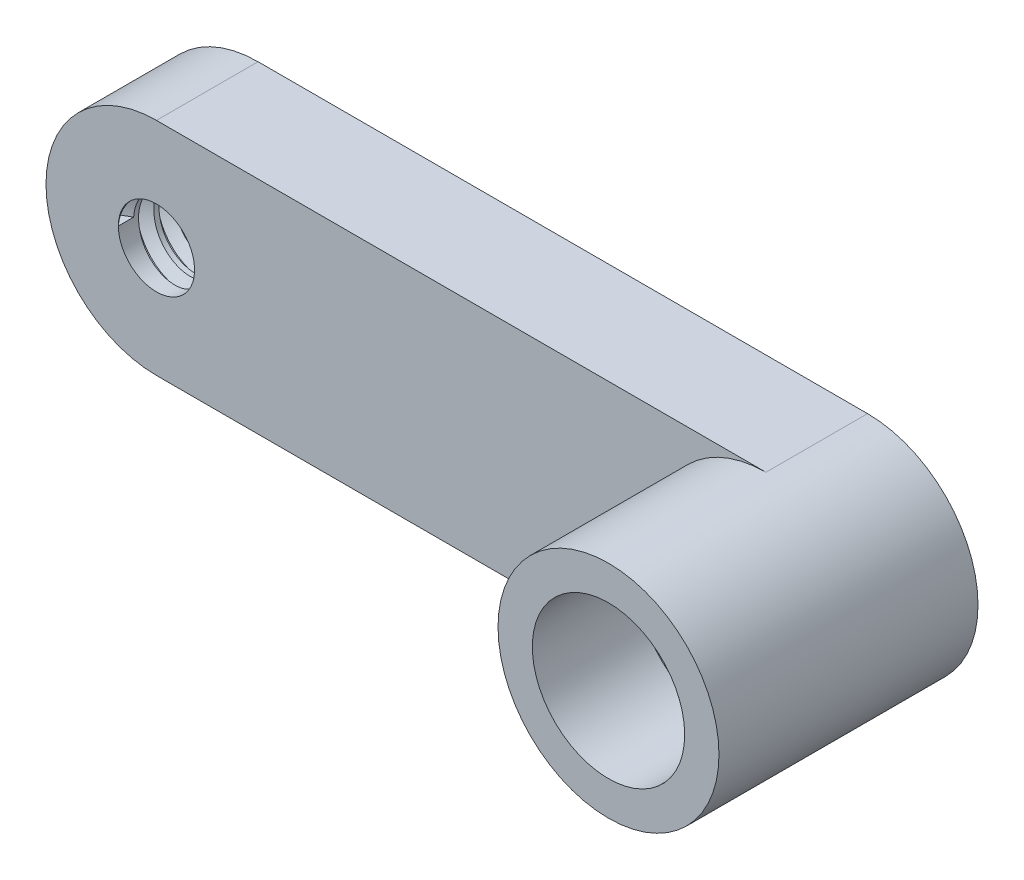
SolidWorks part; units mm, degrees
ref_plane "前视基准面" through (0, 0, 0) normal (0, 0, 1) x (1, 0, 0)
ref_plane "上视基准面" through (0, 0, 0) normal (0, 1, 0) x (1, 0, 0)
ref_plane "右视基准面" through (0, 0, 0) normal (1, 0, 0) x (0, 0, -1)
other "Configuration Table"
sketch "草图1" plane through (0, 0, 0) normal (0, 0, 1) x (1, 0, 0)
  circle A0 centre (0, 0) radius 1.5
  circle A1 centre (0, 0) radius 1.7234
  dimension "D1" = 3
extrude "凸台-拉伸1" add sketch "草图1" along normal blind 2.1
ref_axis "基准轴1" through (0, 0, 2.1) along (0, 0, -1)
sketch "草图12" plane through (0, 0, 2.1) normal (0, 0, 1) x (1, 0, 0)
  circle A0 centre (0, 0) radius 1.7234 construction
  circle A1 centre (0, 0) radius 1.7234
  circle A2 centre (0, 0) radius 2.175
  dimension "D1" = 4.35
extrude "凸台-拉伸4" add sketch "草图12" against normal blind 2.1
sketch "草图15" plane through (0, 0, 0) normal (0, 0, -1) x (-1, 0, 0)
  line L0 (0, 2.175) -> (12, 2.175)
  line L1 (0, -2.175) -> (12, -2.175)
  circle A0 centre (0, 0) radius 2.175 construction
  arc A1 (12, 2.175) -> (12, -2.175) centre (12, 0) cw
  circle A3 centre (0, 0) radius 2.175
  arc A4 (0, 2.175) -> (0, -2.175) centre (0, 0) ccw
  dimension "D1" = 12
  dimension "D2" = 0
extrude "凸台-拉伸6" add sketch "草图15" along normal blind 3
sketch "草图16" plane through (0, 0, 0) normal (0, 0, 1) x (1, 0, 0)
  circle A0 centre (0, 0) radius 1
  dimension "D1" = 2
extrude "切除-拉伸10" cut sketch "草图16" against normal through all
sketch "草图17" plane through (0, 0, 0) normal (0, 0, 1) x (1, 0, 0)
  line L2 (0, 2.175) -> (-12, 2.175)
  line L3 (-12, -2.175) -> (0, -2.175)
  line L4 (0, 2.175) -> (-12, 2.175)
  line L5 (-12, -2.175) -> (0, -2.175)
  arc A2 (0, 2.175) -> (0, -2.175) centre (0, 0) ccw
  arc A3 (-12, 2.175) -> (-12, -2.175) centre (-12, 0) ccw
  arc A4 (0, 2.175) -> (0, -2.175) centre (0, 0) ccw
  arc A5 (-12, 2.175) -> (-12, -2.175) centre (-12, 0) ccw
  dimension "D1" = 0
extrude "切除-拉伸11" cut sketch "草图17" against normal blind 1
sketch "草图18" plane through (0, 0, -3) normal (0, 0, -1) x (-1, 0, 0)
  circle A0 centre (12, 0) radius 0.75
  dimension "D1" = 1.5
  dimension "D2" = 12
extrude "切除-拉伸12" cut sketch "草图18" against normal through all
cosmetic thread "装饰螺纹线1" parameters "D2"=2
thread "螺纹线1" pitch 0.4 method cut profile "螺纹线轮廓1" start angle 0, offset 0, length 10, pitch 0.4, diameter 1.5
ref_plane "基准面1" through (-12.75, 0, -1) normal (0, -1, 0) x (-1, 0, 0)
sketch "螺纹线轮廓1" plane through (-12.75, 0, -1) normal (0, -1, 0) x (-1, 0, 0)
  line L0 (0, 0) -> (0, 0.4) construction
  line L1 (0, 0) -> (0.2165, 0.125)
  line L2 (0.2165, 0.125) -> (0.2165, 0.175)
  line L3 (0.2165, 0.175) -> (0, 0.3)
  line L4 (0.2165, 0.15) -> (0, 0.15) construction
  line L11 (0, 0) -> (0, 0.3)
  point P2 (0, 0)
  dimension "Pitch" = 0.4
  dimension "Profile_Angle" = 60
  dimension "Profile_Land" = 0.05
  dimension "Profile_Height" = 0.2165
